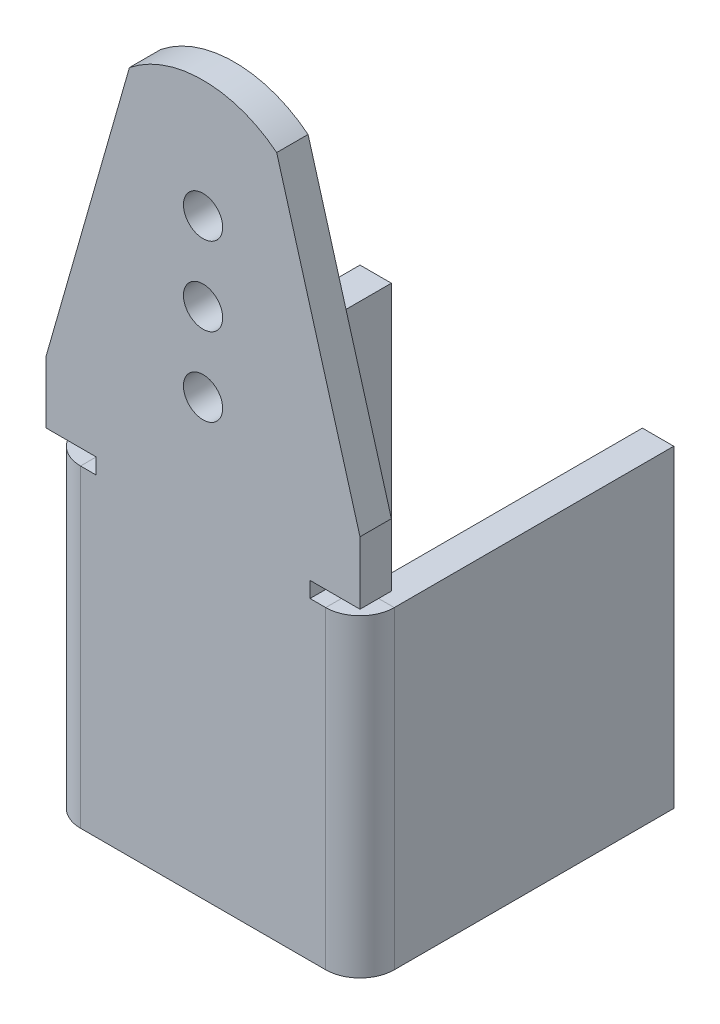
SolidWorks part; units mm, degrees
note: The reader was unsure of these and kept them because the rebuilt part matched: flange length of "边线-法兰10", "边线-法兰12".
ref_plane "前视基准面" through (0, 0, 0) normal (0, 0, 1) x (1, 0, 0)
ref_plane "上视基准面" through (0, 0, 0) normal (0, 1, 0) x (1, 0, 0)
ref_plane "右视基准面" through (0, 0, 0) normal (1, 0, 0) x (0, 0, -1)
sketch "草图1" plane through (0, 0, 0) normal (0, 0, 1) x (1, 0, 0)
  line L1 (0, 0) -> (80, 0)
  line L2 (0, 0) -> (0, 100)
  line L4 (80, 0) -> (80, 100)
  line L8 (0, 100) -> (21.21, 174.2231)
  line L9 (58.758, 174.2231) -> (80, 100)
  arc A1 (21.21, 174.2231) -> (58.758, 174.2231) centre (39.984, 150.8236) cw
  circle A2 centre (39.984, 150.8236) radius 5
  circle A3 centre (39.984, 130.8236) radius 5
  circle A4 centre (39.984, 110.8236) radius 5
  dimension "D3" = 3
  dimension "D6" = 10
  dimension "D7" = 30
  dimension "D1" = 100
  dimension "D2" = 80
  dimension "D4" = 74.2231
  dimension "D5" = 20
ref_plane "基准面2" through (80, 0, 0) normal (1, 0, 0) x (0, 0, -1)
base flange "基体-法兰2" sketch "草图1" thickness 8 reverse thickness direction no parameters "D1"=0.7366
edge flange "边线-法兰10" sketch "草图54" flange angle 90 flange length 80 flange position material inside bend radius 0.7366 thickness 8 relief rectangular parameters "D6"=10
sketch "草图54" plane through (80, 0, -8) normal (-1, 0, 0) x (0, 1, 0)
  line L2 (0, 0) -> (0, 72)
  line L3 (0, 72) -> (80, 72)
  line L4 (80, 72) -> (80, 0)
  line L13 (100, 0) -> (0, 0) construction
  line L14 (80, 0) -> (0, 0)
bend "边线折弯10" bend radius 0.7366 bend angle 90 parameters "D5"=4
edge flange "边线-法兰12" sketch "草图63" flange angle 90 flange length 80 flange position material inside bend radius 0.7366 thickness 8 relief rectangular parameters "D6"=10
sketch "草图63" plane through (0, 0, -8) normal (1, 0, 0) x (0, -1, 0)
  line L2 (-80, 0) -> (-80, 72)
  line L3 (-80, 72) -> (0, 72)
  line L4 (0, 72) -> (0, 0)
  line L5 (0, 0) -> (-100, 0) construction
  line L6 (0, 0) -> (-80, 0)
bend "边线折弯12" bend radius 0.7366 bend angle 90 parameters "D5"=5
sketch "草图64" plane through (0, 0, 0) normal (0, -1, 0) x (1, 0, 0)
  line L1 (0, -40) -> (80, -40) construction
  line L2 (80, -80) -> (80, -8.7366) construction
  line L3 (40, 0) -> (40, -80) construction
  line L4 (8.7366, 0) -> (71.2634, 0) construction
  circle A0 centre (40, -40) radius 10
sketch "折弯-线3" [suppressed] plane through (0, 0, 0) normal (0, 1, 0) x (1, 0, 0)
sketch "边界框3" [suppressed] plane through (0, 0, 0) normal (0, 1, 0) x (1, 0, 0)
sheet metal parameters "钣金7" thickness 8 parameters "D1"=0.7366
flat pattern "平展型式7" [suppressed]
sketch "折弯-线4"
sketch3d "边界框4" [suppressed]
  line L0 (40.016, -570.8779, 0) -> (40.016, 30, 0) construction
  line L1 (-39.984, -570.8779, 0) -> (-39.984, 30, 0) construction
  line L2 (40.016, -570.8779, 0) -> (-39.984, -570.8779, 0) construction
  line L3 (40.016, 30, 0) -> (-39.984, 30, 0) construction
sheet metal parameters "钣金18" thickness 8 parameters "D1"=0.7366
flat pattern "平展型式7"
sketch "折弯-线4" plane through (0, 0, 0) normal (0, 0, 1) x (1, 0, 0)
  line L2 (74.9835, 0) -> (74.9835, 100) construction
  line L3 (74.9835, 0) -> (74.9835, 100) construction
sketch3d "边界框4" [suppressed]
  line L0 (109.983, -150.8236, 0) -> (109.983, 30, 0) construction
  line L1 (-39.984, -150.8236, 0) -> (-39.984, 30, 0) construction
  line L2 (109.983, -150.8236, 0) -> (-39.984, -150.8236, 0) construction
  line L3 (109.983, 30, 0) -> (-39.984, 30, 0) construction
bend of the flat pattern "展平-<边线折弯10>1"
sheet metal parameters "钣金24" thickness 8 parameters "D1"=0.7366
flat pattern "平展型式7"
sketch "折弯-线4" plane through (0, 0, 0) normal (0, 0, 1) x (1, 0, 0)
  line L0 (5.0165, 80) -> (5.0165, 0) construction
  line L1 (5.0165, 80) -> (5.0165, 0) construction
  line L2 (74.9835, 0) -> (74.9835, 80) construction
  line L3 (74.9835, 0) -> (74.9835, 80) construction
sketch3d "边界框4" [suppressed]
  line L0 (-109.951, 30, 0) -> (109.983, 30, 0) construction
  line L1 (-109.951, -150.8236, 0) -> (109.983, -150.8236, 0) construction
  line L2 (-109.951, 30, 0) -> (-109.951, -150.8236, 0) construction
  line L3 (109.983, 30, 0) -> (109.983, -150.8236, 0) construction
bend of the flat pattern "展平-<边线折弯10>1"
bend of the flat pattern "展平-<边线折弯12>1"
